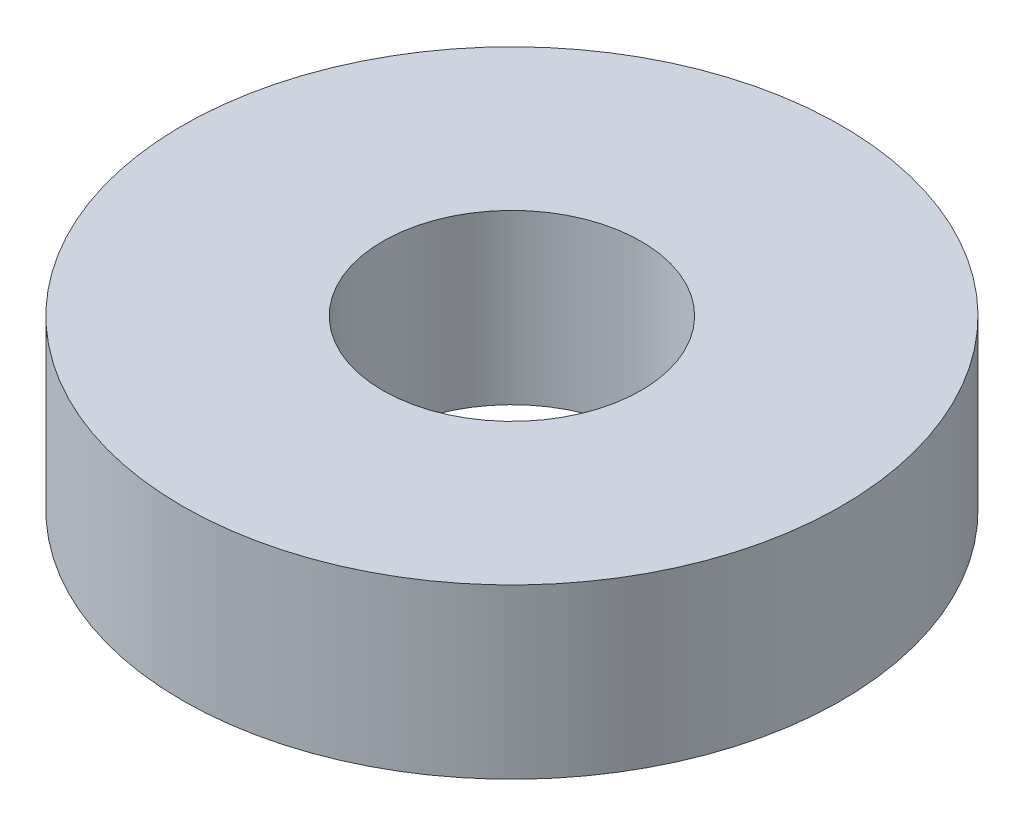
SolidWorks part; units mm, degrees
ref_plane "Front Plane" through (0, 0, 0) normal (0, 0, 1) x (1, 0, 0)
ref_plane "Top Plane" through (0, 0, 0) normal (0, 1, 0) x (1, 0, 0)
ref_plane "Right Plane" through (0, 0, 0) normal (1, 0, 0) x (0, 0, -1)
sketch "Sketch1" plane through (0, 0, 0) normal (0, 1, 0) x (1, 0, 0)
  circle A0 centre (0, 0) radius 3.225
  circle A1 centre (0, 0) radius 8.225
  dimension "D1" = 6.45
  dimension "D2" = 16.45
extrude "Boss-Extrude1" add sketch "Sketch1" along normal blind 4.2
equation "\"D2@Sketch1\"=\"D1@Sketch1\"+10"
